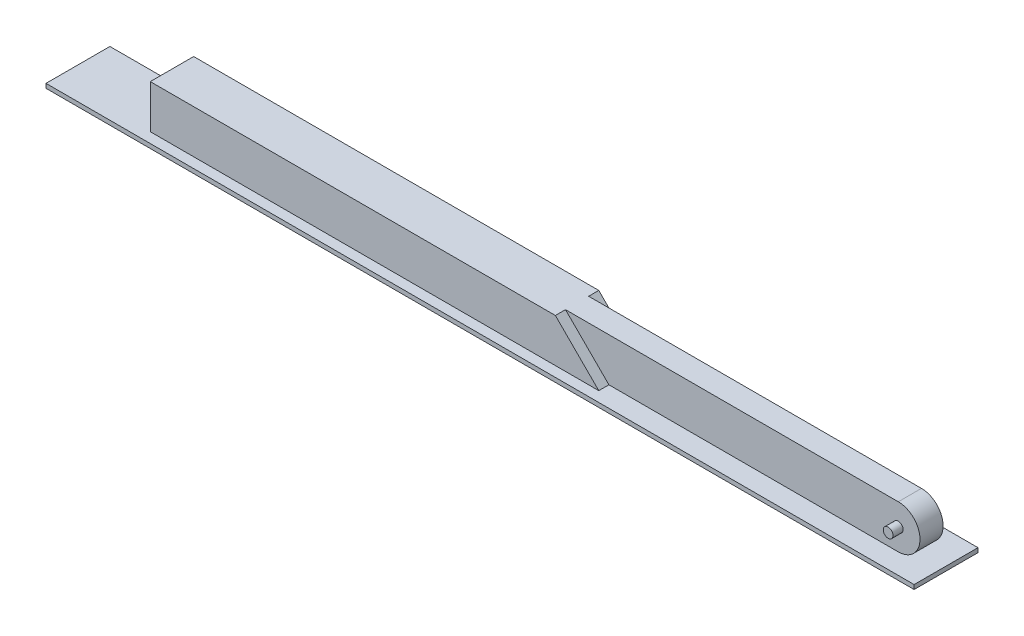
SolidWorks part; units mm, degrees
material "1060 Alloy"
ref_plane "Front Plane" through (0, 0, 0) normal (0, 0, 1) x (1, 0, 0)
ref_plane "Top Plane" through (0, 0, 0) normal (0, 1, 0) x (1, 0, 0)
ref_plane "Right Plane" through (0, 0, 0) normal (1, 0, 0) x (0, 0, -1)
sketch "Sketch1" plane through (0, 0, 0) normal (0, 0, 1) x (1, 0, 0)
  line L0 (-225, 0) -> (225, 0) construction
  line L1 (-225, 15) -> (225, 15)
  line L2 (-225, -15) -> (225, -15)
  arc A0 (-225, 15) -> (-225, -15) centre (-225, 0) ccw
  arc A1 (225, -15) -> (225, 15) centre (225, 0) ccw
  point P2 (0, 0)
  dimension "D1" = 450
  dimension "D2" = 30
extrude "Boss-Extrude1" add sketch "Sketch1" along normal mid plane 30
hole_wizard "H (0.266) Diameter Hole1" positions "Sketch2" profile "Sketch4" hole size "H" standard "ANSI Inch" end condition through all
sketch "Sketch2" plane through (0, 0, 15) normal (0, 0, 1) x (1, 0, 0)
  point P0 (-225, 0)
  point P3 (225, 0)
sketch "Sketch4" plane through (-225, 0, 15) normal (1, 0, 0) x (0, -1, 0)
  line L0 (0, 0) -> (0, 30)
  line L1 (0, 30) -> (3.3782, 30)
  line L2 (3.3782, 30) -> (3.3782, 0)
  line L5 (3.3782, 0) -> (0, 0)
  line L11 (0, -6.35) -> (0, 107.95) construction
  dimension "Thru Hole Dia." = 6.7564
  dimension "Thru Hole Depth" = 30
sketch "Sketch5" plane through (0, 15, 0) normal (0, 1, 0) x (1, 0, 0)
  line L1 (-257, 8) -> (-217, 8)
  line L2 (-257, 8) -> (-257, -8)
  line L3 (-257, -8) -> (-217, -8)
  line L4 (-217, 8) -> (-217, -8)
  line L5 (-217, 0) -> (0, 0) construction
  line L6 (-225, -15) -> (-225, 15) construction
  line L7 (225, -15) -> (225, 15) construction
  line L8 (25, 28.9161) -> (257, 28.9161)
  line L9 (25, 28.9161) -> (25, 8)
  line L10 (25, 8) -> (257, 8)
  line L11 (257, 28.9161) -> (257, 8)
  line L12 (25, -28.9161) -> (257, -28.9161)
  line L13 (25, -28.9161) -> (25, -8)
  line L14 (25, -8) -> (257, -8)
  line L15 (257, -28.9161) -> (257, -8)
  dimension "D1" = 16
  dimension "D2" = 8
  dimension "D3" = 40
  dimension "D4" = 200
  dimension "D5" = 32
extrude "Cut-Extrude1" cut sketch "Sketch5" against normal through all
sketch "Sketch6" plane through (0, 15, 0) normal (0, 1, 0) x (1, 0, 0)
  line L0 (25, 15) -> (25, 8) construction
  line L1 (-412.0368, 59.0418) -> (-175, 59.0418)
  line L2 (-412.0368, 59.0418) -> (-412.0368, -68.39)
  line L3 (-412.0368, -68.39) -> (-175, -68.39)
  line L4 (-175, 59.0418) -> (-175, -68.39)
  dimension "D1" = 200
extrude "Cut-Extrude2" cut sketch "Sketch6" against normal through all
sketch "Sketch10" plane through (-175, 0, 0) normal (-1, 0, 0) x (0, 0, 1)
  line L1 (15, -15) -> (-15, -15)
  line L2 (15, -15) -> (15, 15)
  line L3 (15, 15) -> (-15, 15)
  line L4 (-15, -15) -> (-15, 15)
  line L5 (15, -15) -> (-15, 15) construction
  line L6 (15, 15) -> (-15, -15) construction
  point P0 (0, 0)
extrude "Boss-Extrude3" add sketch "Sketch10" along normal blind 300
sketch "Sketch11" plane through (-475, 0, 0) normal (-1, 0, 0) x (0, 0, 1)
  line L0 (8, -15) -> (-8, -15) construction
  circle A0 centre (0, 3) radius 6.35
  dimension "D1" = 12.7
  dimension "D2" = 18
extrude "Cut-Extrude4" cut sketch "Sketch11" against normal blind 400
sketch "Sketch13" plane through (0, -15, 0) normal (0, -1, 0) x (-1, 0, 0)
  line L0 (-250.0157, 22.0795) -> (-250.0157, -22.0795) construction
  line L1 (349.98, -22.0795) -> (-250.02, -22.0795)
  line L2 (349.98, -22.0795) -> (349.98, 22.0795)
  line L3 (349.98, 22.0795) -> (-250.02, 22.0795)
  line L4 (-250.02, -22.0795) -> (-250.02, 22.0795)
  line L7 (-225, -8) -> (-225, 8) construction
  line L8 (-250.02, 0) -> (0, 0) construction
  point P0 (0, 0)
  dimension "D1" = 600
  dimension "D2" = 25.02
extrude "Boss-Extrude4" add sketch "Sketch13" along normal blind 3
sketch "Sketch14" plane through (0, 15, 0) normal (0, 1, 0) x (1, 0, 0)
  line L0 (225, -8) -> (225, 8) construction
  line L1 (-553.1047, 66.2219) -> (-285, 66.2219)
  line L2 (-553.1047, 66.2219) -> (-553.1047, -58.394)
  line L3 (-553.1047, -58.394) -> (-285, -58.394)
  line L4 (-285, 66.2219) -> (-285, -58.394)
  dimension "D1" = 510
  dimension "D2" = 268.1047
extrude "Cut-Extrude5" cut sketch "Sketch14" against normal up to surface (30 mm away) up to face at (-29.1567, -15, 0)
sketch "Sketch15" plane through (-285, 0, 0) normal (-1, 0, 0) x (0, 0, 1)
  line L1 (-6.35, -3.35) -> (6.35, -3.35)
  line L2 (-6.35, -3.35) -> (-6.35, 9.35)
  line L3 (-6.35, 9.35) -> (6.35, 9.35)
  line L4 (6.35, -3.35) -> (6.35, 9.35)
  line L5 (-6.35, -3.35) -> (6.35, 9.35) construction
  line L6 (-6.35, 9.35) -> (6.35, -3.35) construction
  point P0 (0, 3)
  dimension "D1" = 12.7
extrude "Cut-Extrude6" cut sketch "Sketch15" against normal blind 385
sketch "Sketch16" plane through (0, 0, 0) normal (0, 0, 1) x (1, 0, 0)
  circle A0 centre (225, 0) radius 3.3782
extrude "Boss-Extrude5" add sketch "Sketch16" along normal up to surface and the other way up to surface up to face at (-130, 0, 15) other way up to face at (-130, 0, -15)
chamfer "Chamfer1" distance 30 angle 45 2 edges at (25, 15, 11.5) (25, 15, -11.5)
